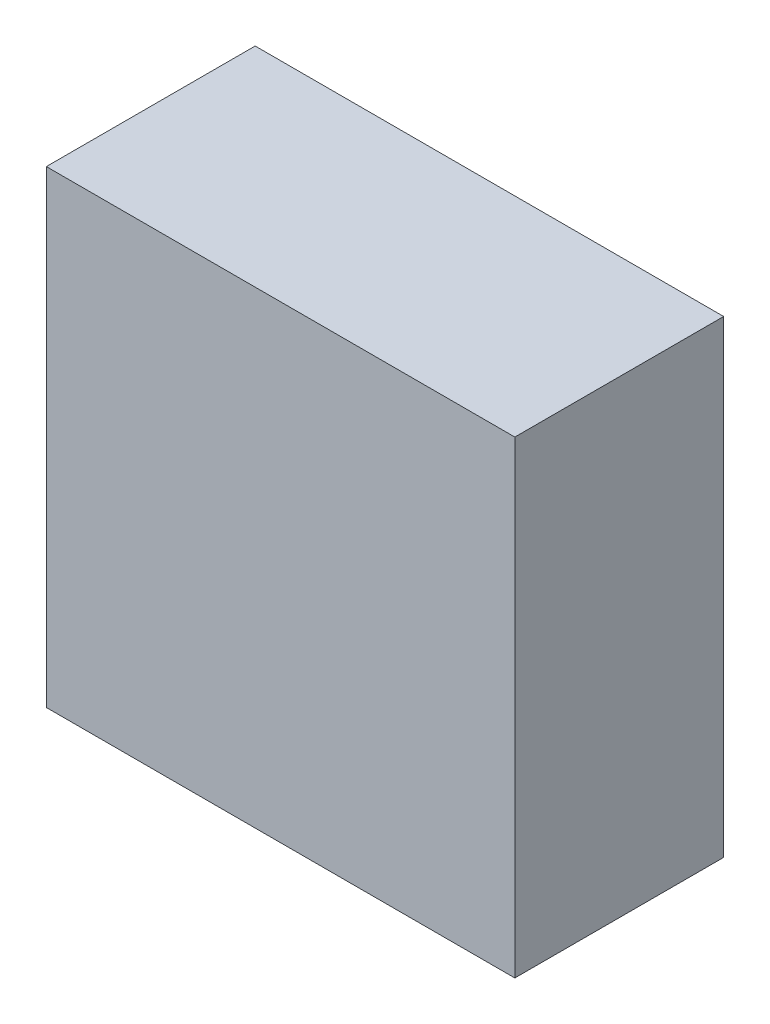
SolidWorks part; units mm, degrees
ref_plane "Front Plane" through (0, 0, 0) normal (0, 0, 1) x (1, 0, 0)
ref_plane "Top Plane" through (0, 0, 0) normal (0, 1, 0) x (1, 0, 0)
ref_plane "Right Plane" through (0, 0, 0) normal (1, 0, 0) x (0, 0, -1)
sketch "Sketch1" plane through (0, 0, 0) normal (0, 0, 1) x (1, 0, 0)
  line L1 (0, 0) -> (59, 0)
  line L2 (0, 0) -> (0, 59)
  line L3 (0, 59) -> (59, 59)
  line L4 (59, 0) -> (59, 59)
  point P5 (-111.6194, -242.6808)
extrude "Boss-Extrude1" add sketch "Sketch1" along normal blind 26.3
